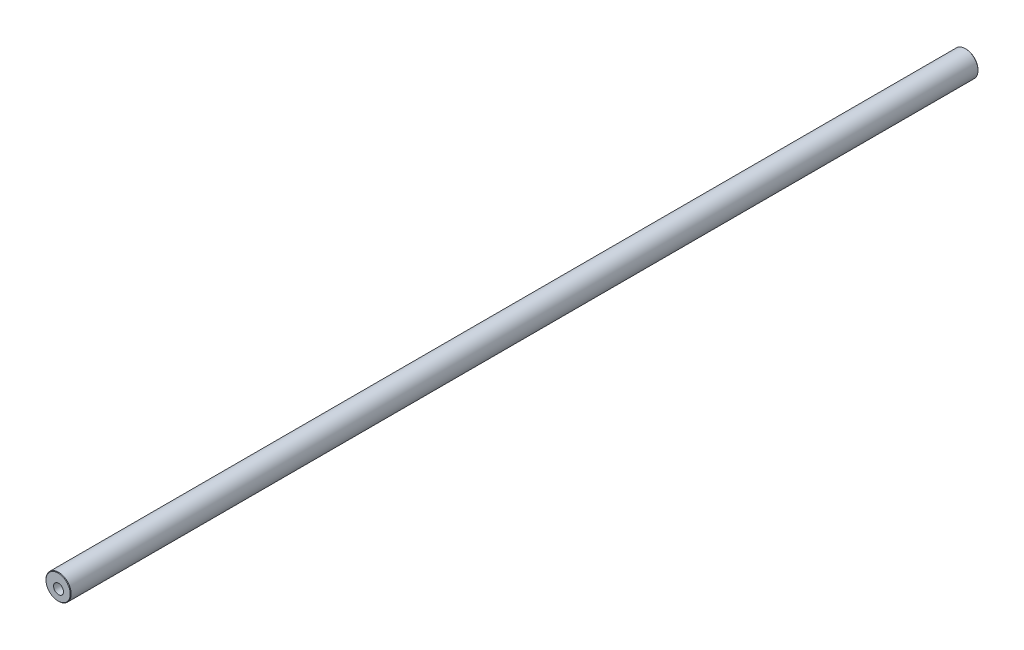
SolidWorks part; units mm, degrees
ref_plane "Front Plane" through (0, 0, 0) normal (0, 0, 1) x (1, 0, 0)
ref_plane "Top Plane" through (0, 0, 0) normal (0, 1, 0) x (1, 0, 0)
ref_plane "Right Plane" through (0, 0, 0) normal (1, 0, 0) x (0, 0, -1)
sketch "Sketch1" plane through (0, 0, 0) normal (0, 0, 1) x (1, 0, 0)
  circle A0 centre (0, 0) radius 6.35 construction
  dimension "Diameter" = 12.7
sketch "Sketch2" plane through (0, 0, 0) normal (1, 0, 0) x (0, 0, -1)
  line L0 (228.6, 0) -> (-228.6, 0) construction
  point P0 (-182.88, 0)
  point P3 (0, 0)
  point P4 (182.88, 0)
  point P6 (-160.02, 0)
  point P7 (160.02, 0)
  dimension "Length" = 457.2
  dimension "D1" = 45.72
  dimension "D2" = 45.72
  dimension "D3" = 68.58
  dimension "D4" = 68.58
sketch "Sketch3" plane through (0, 0, 0) normal (0, 0, 1) x (1, 0, 0)
  circle A0 centre (0, 0) radius 6.35 construction
  circle A1 centre (0, 0) radius 6.35
extrude "Boss-Extrude1" add sketch "Sketch3" along normal up to vertex (228.6 mm away) and the other way up to vertex (228.6 mm away) up to point (0, 0, 228.6) other way up to point (0, 0, -228.6)
chamfer "Chamfer1" distance 0.254 angle 45 2 edges at (6.35, 0, 228.6) (6.35, 0, -228.6)
hole_wizard "M6x1.0 Tapped Hole1" positions "3DSketch1" profile "Sketch6" tap size "M6x1.0" standard "ANSI Metric"
sketch3d "3DSketch1"
  line L0 (0, 0, -228.346) -> (0, 0, -228.6) construction
  point P0 (0, 0, -228.6)
  point P4 (0.2317, -0.7048, 228.6)
sketch "Sketch6" plane through (0, 0, -228.6) normal (1, 0, 0) x (0, 1, 0)
  line L0 (0, 0) -> (0, 26.5022)
  line L1 (0, 26.5022) -> (2.5, 25)
  line L2 (2.5, 25) -> (2.5, 0)
  line L5 (2.5, 0) -> (0, 0)
  line L10 (0, 26.5022) -> (-2.5, 25) construction
  line L11 (0, -6.35) -> (0, 107.95) construction
  dimension "Tap Drill Dia." = 5
  dimension "Tap Drill Depth" = 25
  dimension "Drill Angle" = 118
cosmetic thread "Hole Thread1"
cosmetic thread "Hole Thread2"
equation "\"D1@Chamfer1\"=\"Diameter@Sketch1\"*.02"
equation "\"D1@Sketch2\"=\"D2@Sketch2\""
equation "\"D2@Sketch2\"=\"Length@Sketch2\"*.1"
equation "\"D3@Sketch2\"=\"Length@Sketch2\"*.15"
equation "\"D4@Sketch2\"=\"D3@Sketch2\""
